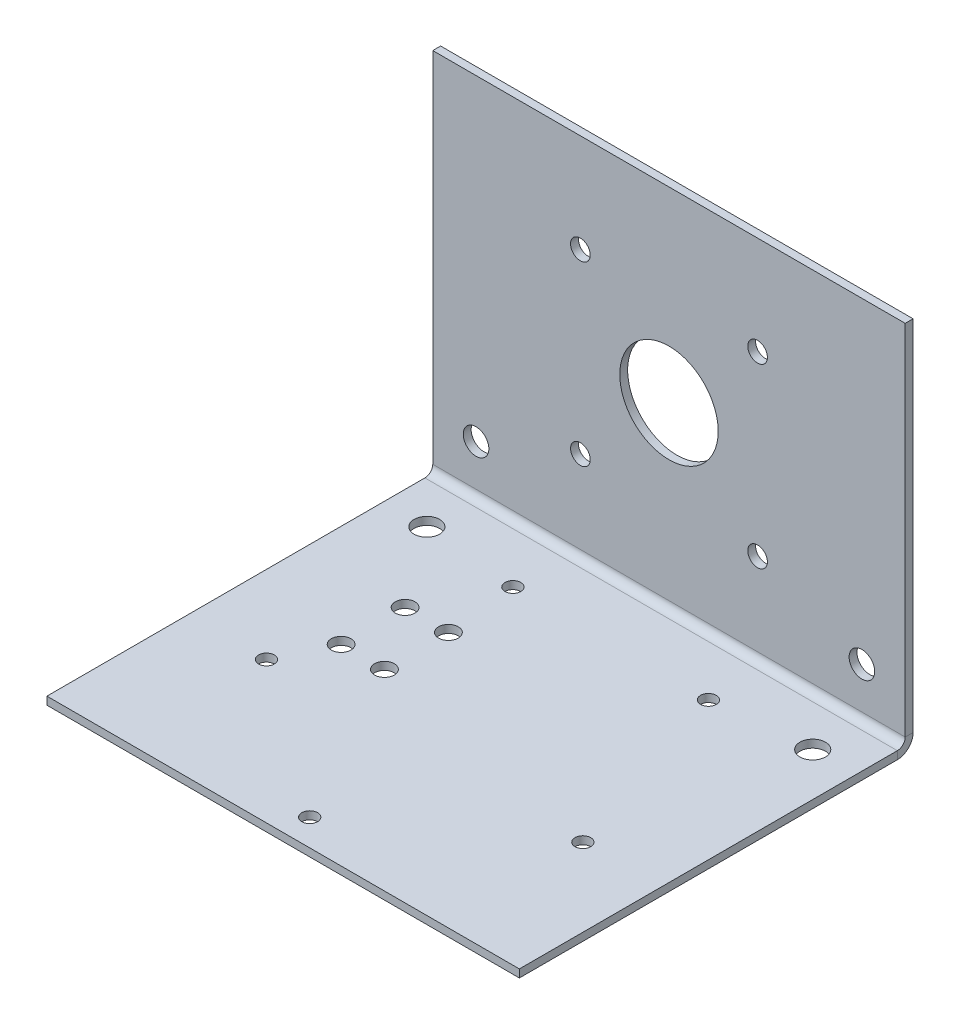
SolidWorks part; units mm, degrees
note: The reader was unsure of these and kept them because the rebuilt part matched: flange length of "Edge-Flange1".
ref_plane "Front Plane" through (0, 0, 0) normal (0, 0, 1) x (1, 0, 0)
ref_plane "Top Plane" through (0, 0, 0) normal (0, 1, 0) x (1, 0, 0)
ref_plane "Right Plane" through (0, 0, 0) normal (1, 0, 0) x (0, 0, -1)
sketch "Sketch2" plane through (0, 0, 0) normal (0, 0, 1) x (1, 0, 0)
  line L0 (60, 95) -> (60, 0) construction
  line L1 (0, 0) -> (120, 0)
  line L2 (0, 0) -> (0, 95)
  line L3 (0, 95) -> (120, 95)
  line L4 (120, 0) -> (120, 95)
  line L5 (37.5, 70) -> (82.5, 70) construction
  line L6 (82.5, 70) -> (82.5, 25) construction
  line L7 (82.5, 25) -> (37.5, 25) construction
  line L8 (37.5, 25) -> (37.5, 70) construction
  line L9 (60, 70) -> (60, 47.5) construction
  line L10 (37.5, 70) -> (82.5, 25) construction
  circle A0 centre (60, 47.5) radius 12.5
  circle A1 centre (82.5, 70) radius 2.5
  circle A2 centre (37.5, 70) radius 2.5
  circle A3 centre (37.5, 25) radius 2.5
  circle A4 centre (82.5, 25) radius 2.5
  circle A5 centre (11, 14.5) radius 3.25
  circle A6 centre (109, 14.5) radius 3.25
  dimension "D3" = 25
  dimension "D4" = 5
  dimension "D5" = 22.5
  dimension "D6" = 14.5
  dimension "D7" = 11
  dimension "D8" = 6.5
  dimension "D1" = 95
  dimension "D2" = 120
base flange "Base-Flange1" sketch "Sketch2" thickness 2 reverse thickness direction no parameters "D1"=0.7366
edge flange "Edge-Flange1" sketch "Sketch9" flange angle 90 flange length 100 flange position material inside bend radius 2 thickness 2 relief rectangular parameters "D6"=10
sketch "Sketch9" plane through (0, 0, 0) normal (0, -1, 0) x (1, 0, 0)
  line L0 (0, 0) -> (120, 0) construction
  line L1 (0, 0) -> (120, 0)
  line L2 (0, 0) -> (0, 98)
  line L3 (0, 98) -> (120, 98)
  line L4 (120, 98) -> (120, 0)
  line L5 (0, 98) -> (120, 0) construction
  line L6 (60, 49) -> (60, 0) construction
  circle A0 centre (60, 49) radius 42.25 construction
  circle A1 centre (60, 91.25) radius 2
  circle A2 centre (100.1821, 62.056) radius 2
  circle A3 centre (84.8339, 14.819) radius 2
  circle A4 centre (35.1661, 14.819) radius 2
  circle A5 centre (19.8179, 62.056) radius 2
  circle A6 centre (109, 12.5) radius 3.25
  circle A7 centre (11, 12.5) radius 3.25
  circle A10 centre (36.98, 33) radius 2.5
  circle A11 centre (25.98, 33) radius 2.5
  circle A12 centre (25.98, 49.25) radius 2.5
  circle A13 centre (36.98, 49.25) radius 2.5
  point P18 (60, 49)
  dimension "D2" = 84.5
  dimension "D3" = 4
  dimension "D5" = 6.5
  dimension "D6" = 11
  dimension "D7" = 12.5
  dimension "D8" = 25.98
  dimension "D9" = 5
  dimension "D10" = 33
  dimension "D11" = 11
  dimension "D12" = 16.25
  dimension "D1" = 98
  dimension "D4" = 5
bend "EdgeBend1" bend radius 2 bend angle 90 parameters "D5"=1
sketch "Bend-Lines1" [suppressed] plane through (0, 0, 0) normal (0, 1, 0) x (1, 0, 0)
sketch "Bounding-Box1" [suppressed] plane through (0, 0, 0) normal (0, 1, 0) x (1, 0, 0)
sheet metal parameters "Sheet-Metal1" thickness 2 parameters "D1"=0.7366
flat pattern "Flat-Pattern1" [suppressed]
sketch "Bend-Lines2" plane through (0, 0, 0) normal (0, 1, 0) x (1, 0, 0)
sketch3d "Bounding-Box2" [suppressed]
  line L0 (0, 0, 0) -> (100, 0, 0) construction
  line L1 (0, 90, 0) -> (100, 90, 0) construction
  line L2 (0, 0, 0) -> (0, 90, 0) construction
  line L3 (100, 0, 0) -> (100, 90, 0) construction
sheet metal parameters "Sheet-Metal2" thickness 2 parameters "D1"=0.7366
flat pattern "Flat-Pattern1"
sketch "Bend-Lines2" plane through (0, 0, 0) normal (0, 0, 1) x (1, 0, 0)
  line L0 (0, 1.6438) -> (120, 1.6438) construction
  line L1 (0, 1.6438) -> (120, 1.6438) construction
sketch3d "Bounding-Box2" [suppressed]
  line L0 (120, 95, 0) -> (120, -96.7124, 0) construction
  line L1 (0, 95, 0) -> (0, -96.7124, 0) construction
  line L2 (120, 95, 0) -> (0, 95, 0) construction
  line L3 (120, -96.7124, 0) -> (0, -96.7124, 0) construction
bend of the flat pattern "Flatten-<EdgeBend1>1"
